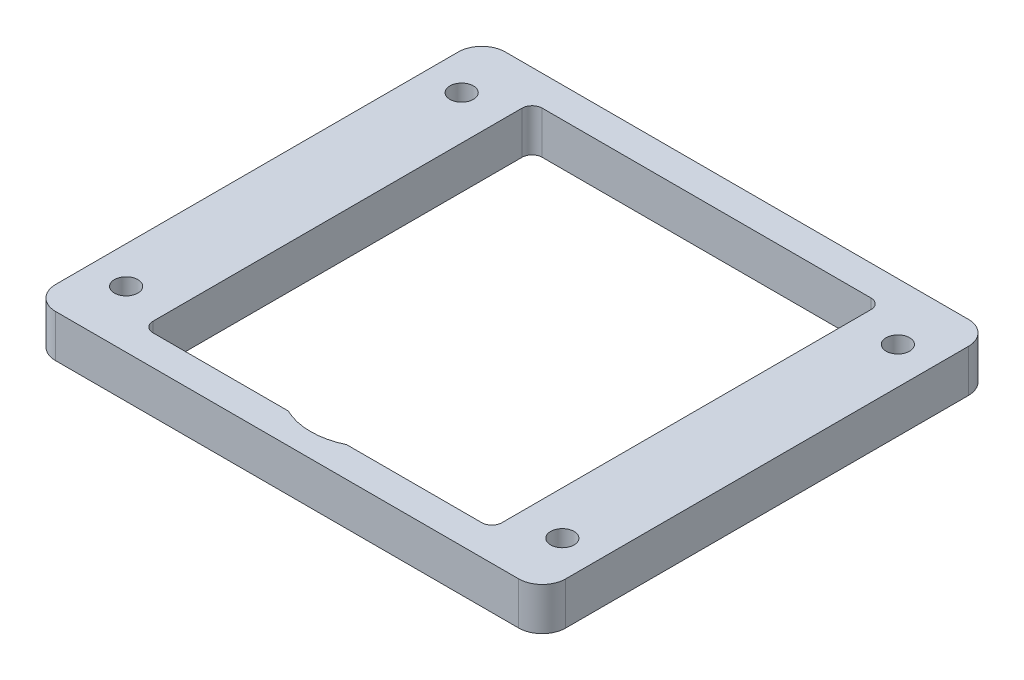
SolidWorks part; units mm, degrees
material "Delrin 150"
ref_plane "Front Plane" through (0, 0, 0) normal (0, 0, 1) x (1, 0, 0)
ref_plane "Top Plane" through (0, 0, 0) normal (0, 1, 0) x (1, 0, 0)
ref_plane "Right Plane" through (0, 0, 0) normal (1, 0, 0) x (0, 0, -1)
ref_axis "Axis1" through (0, 0, -88.99) along (0, 0, 1)
ref_axis "Axis2" through (0, -55, 0) along (0, 1, 0)
ref_axis "Axis3" through (-88.99, 0, 0) along (1, 0, 0)
sketch "Sketch1" plane through (0, 0, 0) normal (0, 1, 0) x (1, 0, 0)
  line L1 (34.5, -33.5) -> (-34.5, -33.5)
  line L2 (38, -30) -> (38, 30)
  line L3 (34.5, 33.5) -> (-34.5, 33.5)
  line L4 (-38, -30) -> (-38, 30)
  line L5 (38, -33.5) -> (-38, 33.5) construction
  line L6 (38, 33.5) -> (-38, -33.5) construction
  line L7 (24.5, -29) -> (-24.5, -29)
  line L8 (26, -27.5) -> (26, 27.5)
  line L9 (24.5, 29) -> (-24.5, 29)
  line L10 (-26, -27.5) -> (-26, 27.5)
  line L11 (26, -29) -> (-26, 29) construction
  line L12 (26, 29) -> (-26, -29) construction
  arc A0 (26, 27.5) -> (24.5, 29) centre (24.5, 27.5) ccw
  arc A1 (24.5, -29) -> (26, -27.5) centre (24.5, -27.5) ccw
  arc A2 (-24.5, -29) -> (-26, -27.5) centre (-24.5, -27.5) cw
  arc A3 (-24.5, 29) -> (-26, 27.5) centre (-24.5, 27.5) ccw
  arc A4 (38, 30) -> (34.5, 33.5) centre (34.5, 30) ccw
  arc A5 (34.5, -33.5) -> (38, -30) centre (34.5, -30) ccw
  arc A6 (-34.5, -33.5) -> (-38, -30) centre (-34.5, -30) cw
  arc A7 (-34.5, 33.5) -> (-38, 30) centre (-34.5, 30) ccw
  point P0 (0, 0)
  point P6 (0, 0)
  dimension "D5" = 1.5
  dimension "D6" = 3.5
  dimension "D1" = 52
  dimension "D2" = 76
  dimension "D3" = 67
  dimension "D4" = 58
extrude "Boss-Extrude1" add sketch "Sketch1" along normal blind 6.35
hole_wizard "Tap Drill for M5x0.8 Tap1" positions "Sketch3" profile "Sketch2" hole size "M5x0.8" standard "ANSI Metric" end condition through all
sketch "Sketch3" plane through (0, 6.35, 0) normal (0, 1, 0) x (1, 0, 0)
  line L0 (-26, 0) -> (0, 0) construction
  line L1 (-26, 27.5) -> (-26, -27.5) construction
  line L2 (0, 0) -> (0, 33.5) construction
  line L3 (34.5, 33.5) -> (-34.5, 33.5) construction
  point P0 (-32.5, -25)
  point P13 (-32.5, 25)
  point P15 (32.5, -25)
  point P16 (32.5, 25)
  dimension "D1" = 65
  dimension "D2" = 50
sketch "Sketch2" plane through (-32.5, 6.35, 25) normal (1, 0, 0) x (0, 0, 1)
  line L0 (0, 0) -> (0, 6.35)
  line L1 (0, 6.35) -> (1.75, 6.35)
  line L2 (1.75, 6.35) -> (1.75, 0)
  line L5 (1.75, 0) -> (0, 0)
  line L11 (0, -6.35) -> (0, 107.95) construction
  dimension "Thru Hole Dia." = 3.5
  dimension "Thru Hole Depth" = 6.35
sketch "Sketch4" plane through (0, 6.35, 0) normal (0, 1, 0) x (1, 0, 0)
  line L1 (0, -20) -> (0, 0) construction
  line L4 (-24.5, -29) -> (24.5, -29) construction
  circle A0 centre (0, -20) radius 10
  dimension "D1" = 1
  dimension "D2" = 20
extrude "Cut-Extrude1" cut sketch "Sketch4" against normal through all
